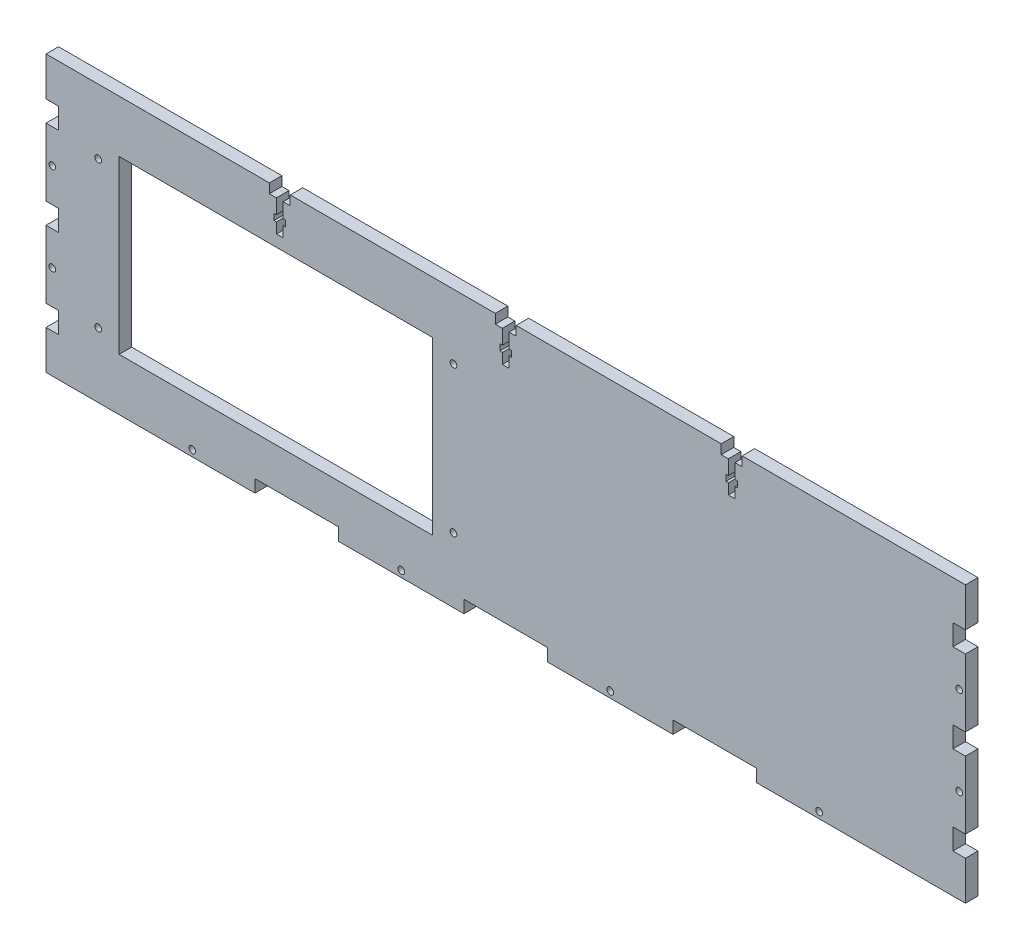
SolidWorks part; units mm, degrees
ref_plane "Front Plane" through (0, 0, 0) normal (0, 0, 1) x (1, 0, 0)
ref_plane "Top Plane" through (0, 0, 0) normal (0, 1, 0) x (1, 0, 0)
ref_plane "Right Plane" through (0, 0, 0) normal (1, 0, 0) x (0, 0, -1)
sketch "Sketch1" plane through (0, 0, 0) normal (0, 0, 1) x (1, 0, 0)
  line L1 (-220, -66) -> (220, -66)
  line L2 (-220, -66) -> (-220, 66)
  line L3 (-220, 66) -> (220, 66)
  line L4 (220, -66) -> (220, 66)
  line L5 (-220, -66) -> (220, 66) construction
  line L6 (-220, 66) -> (220, -66) construction
  point P0 (0, 0)
  dimension "D1" = 440
  dimension "D2" = 132
extrude "Boss-Extrude1" add sketch "Sketch1" along normal blind 6
sketch "Sketch2" plane through (0, 0, 0) normal (0, 0, -1) x (-1, 0, 0)
  line L0 (220, 47.3321) -> (220, 37.3321) construction
  line L1 (220, 37.3321) -> (214, 37.3321) construction
  line L2 (214, 37.3321) -> (214, 47.3321) construction
  line L3 (214, 47.3321) -> (220, 47.3321) construction
  line L12 (220, -37.3321) -> (220, -47.3321) construction
  line L13 (220, -47.3321) -> (214, -47.3321) construction
  line L14 (214, -47.3321) -> (214, -37.3321) construction
  line L15 (214, -37.3321) -> (220, -37.3321) construction
  line L16 (220, 47.3321) -> (220, 37.3321)
  line L17 (220, 37.3321) -> (214, 37.3321)
  line L18 (214, 37.3321) -> (214, 47.3321)
  line L19 (214, 47.3321) -> (220, 47.3321)
  line L20 (220, -37.3321) -> (220, -47.3321)
  line L21 (220, -47.3321) -> (214, -47.3321)
  line L22 (214, -47.3321) -> (214, -37.3321)
  line L23 (214, -37.3321) -> (220, -37.3321)
  line L24 (-214, -37.3321) -> (-214, -47.3321) construction
  line L25 (-214, -47.3321) -> (-220, -47.3321) construction
  line L26 (-220, -47.3321) -> (-220, -37.3321) construction
  line L27 (-220, -37.3321) -> (-214, -37.3321) construction
  line L28 (-214, 47.3321) -> (-214, 37.3321) construction
  line L29 (-214, 37.3321) -> (-220, 37.3321) construction
  line L30 (-220, 37.3321) -> (-220, 47.3321) construction
  line L31 (-220, 47.3321) -> (-214, 47.3321) construction
  line L32 (-214, -37.3321) -> (-214, -47.3321)
  line L33 (-214, -47.3321) -> (-220, -47.3321)
  line L34 (-220, -47.3321) -> (-220, -37.3321)
  line L35 (-220, -37.3321) -> (-214, -37.3321)
  line L36 (-214, 47.3321) -> (-214, 37.3321)
  line L37 (-214, 37.3321) -> (-220, 37.3321)
  line L38 (-220, 37.3321) -> (-220, 47.3321)
  line L39 (-220, 47.3321) -> (-214, 47.3321)
  line L44 (220, -5) -> (220, 5)
  line L45 (214, -5) -> (220, -5)
  line L46 (214, 5) -> (214, -5)
  line L47 (220, 5) -> (214, 5)
  line L48 (220, -5) -> (220, 5)
  line L49 (214, -5) -> (220, -5)
  line L50 (214, 5) -> (214, -5)
  line L51 (220, 5) -> (214, 5)
  line L52 (-214, -5) -> (-214, 5)
  line L53 (-220, -5) -> (-214, -5)
  line L54 (-220, 5) -> (-220, -5)
  line L55 (-214, 5) -> (-220, 5)
  line L56 (-214, -5) -> (-214, 5)
  line L57 (-220, -5) -> (-214, -5)
  line L58 (-220, 5) -> (-220, -5)
  line L59 (-214, 5) -> (-220, 5)
  circle A0 centre (217, 21.1661) radius 1.6 construction
  circle A1 centre (217, -21.1661) radius 1.6 construction
  circle A2 centre (-217, 21.1661) radius 1.6 construction
  circle A3 centre (-217, -21.1661) radius 1.6 construction
  circle A4 centre (217, 21.1661) radius 1.6
  circle A5 centre (217, -21.1661) radius 1.6
  circle A6 centre (-217, 21.1661) radius 1.6
  circle A7 centre (-217, -21.1661) radius 1.6
  dimension "D2" = 0
  dimension "D3" = 0
extrude "Cut-Extrude1" cut sketch "Sketch2" against normal up to next
sketch "Sketch3" plane through (0, 0, 0) normal (0, 0, -1) x (-1, 0, 0)
  circle A0 centre (-150, -63) radius 1.6 construction
  circle A1 centre (-50, -63) radius 1.6 construction
  circle A2 centre (50, -63) radius 1.6 construction
  circle A3 centre (150, -63) radius 1.6 construction
  circle A4 centre (-150, -63) radius 1.6
  circle A5 centre (-50, -63) radius 1.6
  circle A6 centre (50, -63) radius 1.6
  circle A7 centre (150, -63) radius 1.6
extrude "Cut-Extrude2" cut sketch "Sketch3" against normal up to next
sketch "Sketch4" plane through (0, 0, 0) normal (0, 0, -1) x (-1, 0, 0)
  line L0 (80, -66) -> (120, -66) construction
  line L1 (120, -66) -> (120, -60) construction
  line L2 (120, -60) -> (80, -60) construction
  line L3 (80, -60) -> (80, -66) construction
  line L4 (-20, -66) -> (20, -66) construction
  line L5 (20, -66) -> (20, -60) construction
  line L6 (20, -60) -> (-20, -60) construction
  line L7 (-20, -60) -> (-20, -66) construction
  line L8 (-120, -66) -> (-80, -66) construction
  line L9 (-80, -66) -> (-80, -60) construction
  line L10 (-80, -60) -> (-120, -60) construction
  line L11 (-120, -60) -> (-120, -66) construction
  line L12 (80, -66) -> (120, -66)
  line L13 (120, -66) -> (120, -60)
  line L14 (120, -60) -> (80, -60)
  line L15 (80, -60) -> (80, -66)
  line L16 (-20, -66) -> (20, -66)
  line L17 (20, -66) -> (20, -60)
  line L18 (20, -60) -> (-20, -60)
  line L19 (-20, -60) -> (-20, -66)
  line L20 (-120, -66) -> (-80, -66)
  line L21 (-80, -66) -> (-80, -60)
  line L22 (-80, -60) -> (-120, -60)
  line L23 (-120, -60) -> (-120, -66)
extrude "Cut-Extrude3" cut sketch "Sketch4" against normal up to next
sketch "Sketch5" plane through (0, 66, 0) normal (0, 1, 0) x (1, 0, 0)
  line L0 (220, 0) -> (-220, 0) construction
  line L1 (-113.125, -6) -> (-103.125, -6)
  line L2 (-113.125, -6) -> (-113.125, 0)
  line L3 (-113.125, 0) -> (-103.125, 0)
  line L4 (-103.125, -6) -> (-103.125, 0)
  line L5 (-113.125, -6) -> (-103.125, 0) construction
  line L6 (-113.125, 0) -> (-103.125, -6) construction
  line L7 (-103.125, -6) -> (-103.125, 0) construction
  line L8 (5, -6) -> (5, 0) construction
  line L9 (-5, -6) -> (5, -6)
  line L10 (-5, -6) -> (-5, 0)
  line L11 (-5, 0) -> (5, 0)
  line L12 (5, -6) -> (5, 0)
  line L13 (-5, -6) -> (5, 0) construction
  line L14 (-5, 0) -> (5, -6) construction
  line L15 (113.125, -6) -> (113.125, 0) construction
  line L16 (103.125, -6) -> (113.125, -6)
  line L17 (103.125, -6) -> (103.125, 0)
  line L18 (103.125, 0) -> (113.125, 0)
  line L19 (113.125, -6) -> (113.125, 0)
  line L20 (103.125, -6) -> (113.125, 0) construction
  line L21 (103.125, 0) -> (113.125, -6) construction
  point P0 (-108.125, -3)
  point P10 (0, -3)
  point P18 (108.125, -3)
extrude "Cut-Extrude4" cut sketch "Sketch5" against normal blind 4.5
sketch "Sketch6" plane through (0, 0, 0) normal (0, 0, -1) x (-1, 0, 0)
  line L0 (-108.125, 61.5) -> (-108.125, 46.5) construction
  line L1 (-113.125, 61.5) -> (-103.125, 61.5) construction
  line L2 (-109.725, 61.5) -> (-109.725, 54.5)
  line L3 (-106.525, 61.5) -> (-106.525, 54.5)
  line L4 (-109.725, 61.5) -> (-106.525, 61.5)
  line L5 (-109.725, 46.5) -> (-106.525, 46.5)
  line L6 (-106.525, 51.5) -> (-105.325, 51.5)
  line L7 (-110.925, 54.5) -> (-109.725, 54.5)
  line L8 (-110.925, 54.5) -> (-110.925, 51.5)
  line L9 (-110.925, 51.5) -> (-109.725, 51.5)
  line L10 (-105.325, 54.5) -> (-105.325, 51.5)
  line L11 (-110.925, 54.5) -> (-105.325, 51.5) construction
  line L12 (-110.925, 51.5) -> (-105.325, 54.5) construction
  line L13 (-106.525, 51.5) -> (-106.525, 46.5)
  line L14 (-106.525, 61.5) -> (-106.525, 46.5) construction
  line L15 (-109.725, 51.5) -> (-109.725, 46.5)
  line L16 (-109.725, 61.5) -> (-109.725, 46.5) construction
  line L17 (-106.525, 54.5) -> (-105.325, 54.5)
  line L18 (-1.595, 61.5) -> (-1.595, 54.5)
  line L19 (1.605, 61.5) -> (1.605, 54.5)
  line L20 (-1.595, 61.5) -> (1.605, 61.5)
  line L21 (-1.595, 46.5) -> (1.605, 46.5)
  line L22 (1.605, 51.5) -> (2.805, 51.5)
  line L23 (-2.795, 54.5) -> (-1.595, 54.5)
  line L24 (-2.795, 54.5) -> (-2.795, 51.5)
  line L25 (-2.795, 51.5) -> (-1.595, 51.5)
  line L26 (2.805, 54.5) -> (2.805, 51.5)
  line L27 (1.605, 51.5) -> (1.605, 46.5)
  line L28 (-1.595, 51.5) -> (-1.595, 46.5)
  line L29 (1.605, 54.5) -> (2.805, 54.5)
  line L30 (0.005, 61.5) -> (0.005, 46.5) construction
  line L31 (-2.795, 54.5) -> (2.805, 51.5) construction
  line L32 (-2.795, 51.5) -> (2.805, 54.5) construction
  line L33 (106.535, 61.5) -> (106.535, 54.5)
  line L34 (109.735, 61.5) -> (109.735, 54.5)
  line L35 (106.535, 61.5) -> (109.735, 61.5)
  line L36 (106.535, 46.5) -> (109.735, 46.5)
  line L37 (109.735, 51.5) -> (110.935, 51.5)
  line L38 (105.335, 54.5) -> (106.535, 54.5)
  line L39 (105.335, 54.5) -> (105.335, 51.5)
  line L40 (105.335, 51.5) -> (106.535, 51.5)
  line L41 (110.935, 54.5) -> (110.935, 51.5)
  line L42 (109.735, 51.5) -> (109.735, 46.5)
  line L43 (106.535, 51.5) -> (106.535, 46.5)
  line L44 (109.735, 54.5) -> (110.935, 54.5)
  line L45 (108.135, 61.5) -> (108.135, 46.5) construction
  line L46 (105.335, 54.5) -> (110.935, 51.5) construction
  line L47 (105.335, 51.5) -> (110.935, 54.5) construction
  point P8 (-108.125, 53)
  point P25 (0.005, 53)
  point P40 (108.135, 53)
  dimension "D1" = 15
  dimension "D4" = 5.6
  dimension "D5" = 3
  dimension "D6" = 7
  dimension "D2" = 1.6
  dimension "D3" = 1.6
  dimension "D7" = 3
extrude "Cut-Extrude5" cut sketch "Sketch6" against normal up to next
sketch "Sketch7" plane through (0, 0, 0) normal (0, 0, -1) x (-1, 0, 0)
  line L0 (0, 0) -> (220, 0) construction
  line L1 (220, 37.3321) -> (220, 5) construction
  line L2 (113.125, 66) -> (220, 66) construction
  line L3 (35, -41) -> (185, -41)
  line L4 (35, -41) -> (35, 41)
  line L5 (35, 41) -> (185, 41)
  line L6 (185, -41) -> (185, 41)
  line L7 (35, -41) -> (185, 41) construction
  line L8 (35, 41) -> (185, -41) construction
  line L9 (25, 35) -> (25, -35) construction
  line L10 (25, 35) -> (195, 35) construction
  line L11 (25, -35) -> (35, -35) construction
  line L12 (195, -35) -> (185, -35) construction
  circle A0 centre (25, 35) radius 1.6
  circle A1 centre (25, -35) radius 1.6
  circle A2 centre (195, 35) radius 1.6
  circle A3 centre (195, -35) radius 1.6
  point P3 (110, 0)
  point P4 (110, 0)
  point P21 (110, 35)
  point P22 (25, 0)
  dimension "D5" = 3.2
  dimension "D1" = 25
  dimension "D2" = 150
  dimension "D3" = 10
  dimension "D4" = 70
extrude "Cut-Extrude6" cut sketch "Sketch7" against normal through all
equation "\"m3_depth\"=15"
equation "\"D1@Sketch6\"=\"m3_depth\""
equation "\"m3_nut_width\"=5.6"
equation "\"D4@Sketch6\"=\"m3_nut_width\""
equation "\"m3_nut_thickness\"=3"
equation "\"D5@Sketch6\"=\"m3_nut_thickness\""
equation "\"m3_nut_depth\"=7"
equation "\"D6@Sketch6\"=\"m3_nut_depth\""
